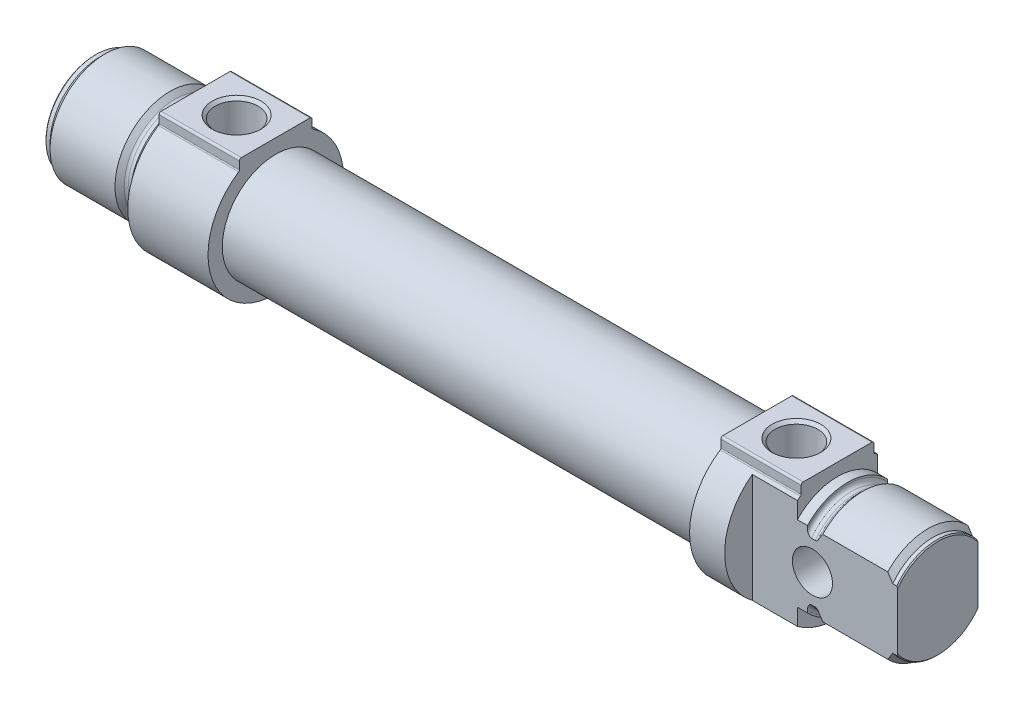
SolidWorks part; units mm, degrees
ref_plane "Front Plane" through (0, 0, 0) normal (0, 0, 1) x (1, 0, 0)
ref_plane "Top Plane" through (0, 0, 0) normal (0, 1, 0) x (1, 0, 0)
ref_plane "Right Plane" through (0, 0, 0) normal (1, 0, 0) x (0, 0, -1)
sketch "Sketch1" plane through (0, 0, 0) normal (0, 0, 1) x (1, 0, 0)
  line L0 (0, 0) -> (0, 9.8)
  line L1 (0, 9.8) -> (0.2, 10)
  line L2 (0.2, 10) -> (1, 10)
  line L3 (1, 10) -> (2, 11)
  line L4 (2, 11) -> (14.95, 11)
  line L5 (14.95, 11) -> (15.8657, 10.0843)
  line L6 (16.4314, 9.85) -> (17.2, 9.85)
  line L7 (18, 10.65) -> (18, 11)
  line L8 (18, 11) -> (20, 11)
  line L9 (20, 11) -> (20, 0)
  line L10 (20, 0) -> (0, 0)
  line L11 (20, 0) -> (0, 0) construction
  arc A0 (15.8657, 10.0843) -> (16.4314, 9.85) centre (16.4314, 10.65) ccw
  arc A1 (17.2, 9.85) -> (18, 10.65) centre (17.2, 10.65) ccw
revolve "Revolve1" add sketch "Sketch1" angle 360 about L11 reverse direction yes
cosmetic thread "Cosmetic Thread1" parameters "D1"=13.87, "D2"=20.16
ref_plane "Plane1" through (28.7, 0, 0) normal (1, 0, 0) x (0, 0, -1)
ref_plane "Plane2" through (10.5, 0, 0) normal (1, 0, 0) x (0, 0, -1)
ref_plane "Plane3" through (0, -14, 0) normal (0, 1, 0) x (1, 0, 0)
ref_plane "Plane4" through (0, 13, 0) normal (0, 1, 0) x (1, 0, 0)
ref_plane "Plane5" through (0, 0, 0) normal (0, 1, 0) x (1, 0, 0)
ref_plane "Plane6" through (0, 0, 0) normal (0, 1, 0) x (1, 0, 0)
ref_plane "Plane7" through (20, 0, 0) normal (1, 0, 0) x (0, 0, -1)
ref_plane "Plane8" through (20, 0, 0) normal (1, 0, 0) x (0, 0, -1)
ref_plane "Plane9" through (33, 0, 0) normal (1, 0, 0) x (0, 0, -1)
ref_plane "Plane10" through (24.5, 0, 0) normal (1, 0, 0) x (0, 0, -1)
ref_plane "Plane11" through (44.5, 0, 0) normal (1, 0, 0) x (0, 0, -1)
sketch "Sketch2" plane through (20, 0, 0) normal (1, 0, 0) x (0, 0, -1)
  line L0 (7.25, 11.5515) -> (7.25, 13.1)
  line L1 (6.85, 13.5) -> (-6.85, 13.5)
  line L2 (-7.25, 13.1) -> (-7.25, 11.5515)
  arc A0 (-7.3859, 11.3004) -> (7.3859, 11.3004) centre (0, 0) ccw
  arc A1 (7.3859, 11.3004) -> (7.25, 11.5515) centre (7.55, 11.5515) cw
  arc A2 (7.25, 13.1) -> (6.85, 13.5) centre (6.85, 13.1) ccw
  arc A3 (-6.85, 13.5) -> (-7.25, 13.1) centre (-6.85, 13.1) ccw
  arc A4 (-7.25, 11.5515) -> (-7.3859, 11.3004) centre (-7.55, 11.5515) cw
extrude "Boss-Extrude1" add sketch "Sketch2" along normal blind 16
ref_plane "Plane12" through (32.5, 0, 0) normal (1, 0, 0) x (0, 0, -1)
ref_plane "Plane13" through (0, 0, 0) normal (0, 0, 1) x (1, 0, 0)
ref_plane "Plane14" through (0, 0, -8.5) normal (0, 0, 1) x (1, 0, 0)
ref_plane "Plane15" through (0, 0, 0) normal (0, 1, 0) x (1, 0, 0)
ref_plane "Plane16" through (0, 6.9, 0) normal (0, 1, 0) x (1, 0, 0)
ref_plane "Plane17" through (0, 0, -6.6) normal (0, 0, 1) x (1, 0, 0)
ref_plane "Plane18" through (0, 0, 0) normal (0, 1, 0) x (1, 0, 0)
ref_plane "Plane19" through (0, 6.9, 0) normal (0, 1, 0) x (1, 0, 0)
ref_plane "Plane20" through (0, 7.8206, -1.379) normal (0, 0.9848, -0.1736) x (1, 0, 0)
ref_plane "Plane21" through (0, 6.3434, -1.1185) normal (0, 0.9848, -0.1736) x (1, 0, 0)
sketch "Sketch3" plane through (0, 0, 0) normal (0, 0, 1) x (1, 0, 0)
  line L0 (36, 0) -> (36, 10.65)
  line L1 (36, 10.65) -> (132, 10.65)
  line L2 (132, 10.65) -> (132, 0)
  line L3 (132, 0) -> (36, 0)
  line L4 (132, 0) -> (36, 0) construction
revolve "Revolve2" add sketch "Sketch3" angle 360 about L4 reverse direction yes
ref_plane "Plane22" through (132, 0, 0) normal (1, 0, 0) x (0, 0, -1)
sketch "Sketch4" plane through (132, 0, 0) normal (1, 0, 0) x (0, 0, -1)
  line L0 (7.25, 11.5515) -> (7.25, 13.1)
  line L1 (6.85, 13.5) -> (-6.85, 13.5)
  line L2 (-7.25, 13.1) -> (-7.25, 11.5515)
  arc A0 (-7.3859, 11.3004) -> (7.3859, 11.3004) centre (0, 0) ccw
  arc A1 (7.3859, 11.3004) -> (7.25, 11.5515) centre (7.55, 11.5515) cw
  arc A2 (7.25, 13.1) -> (6.85, 13.5) centre (6.85, 13.1) ccw
  arc A3 (-6.85, 13.5) -> (-7.25, 13.1) centre (-6.85, 13.1) ccw
  arc A4 (-7.25, 11.5515) -> (-7.3859, 11.3004) centre (-7.55, 11.5515) cw
extrude "Boss-Extrude2" add sketch "Sketch4" along normal blind 16
ref_plane "Plane23" through (135.8, 0, 0) normal (1, 0, 0) x (0, 0, -1)
ref_plane "Plane24" through (135.5, 0, 0) normal (1, 0, 0) x (0, 0, -1)
ref_plane "Plane25" through (0, 0, 6.6) normal (0, 0, 1) x (1, 0, 0)
ref_plane "Plane26" through (0, 0, 0) normal (0, 1, 0) x (1, 0, 0)
ref_plane "Plane27" through (0, 6.9, 0) normal (0, 1, 0) x (1, 0, 0)
ref_plane "Plane28" through (0, 7.8206, 1.379) normal (0, 0.9848, 0.1736) x (1, 0, 0)
ref_plane "Plane29" through (0, 6.3434, 1.1185) normal (0, 0.9848, 0.1736) x (1, 0, 0)
ref_plane "Plane30" through (195, 0, 0) normal (1, 0, 0) x (0, 0, -1)
sketch "Sketch5" plane through (0, 0, 0) normal (0, 0, 1) x (1, 0, 0)
  line L0 (148, 0) -> (148, 11)
  line L1 (148, 11) -> (150, 11)
  line L2 (150, 11) -> (150, 10.65)
  line L3 (150.8, 9.85) -> (151.5686, 9.85)
  line L4 (152.1343, 10.0843) -> (153.05, 11)
  line L5 (153.05, 11) -> (166, 11)
  line L6 (166, 11) -> (167, 10)
  line L7 (167, 10) -> (167.8, 10)
  line L8 (167.8, 10) -> (168, 9.8)
  line L9 (168, 9.8) -> (168, 0)
  line L10 (168, 0) -> (148, 0)
  line L11 (168, 0) -> (148, 0) construction
  arc A0 (150, 10.65) -> (150.8, 9.85) centre (150.8, 10.65) ccw
  arc A1 (151.5686, 9.85) -> (152.1343, 10.0843) centre (151.5686, 10.65) ccw
revolve "Revolve3" add sketch "Sketch5" angle 360 about L11 reverse direction yes
cosmetic thread "Cosmetic Thread2" parameters "D1"=12.87, "D2"=20.16
ref_plane "Plane31" through (182, 0, 0) normal (1, 0, 0) x (0, 0, -1)
ref_plane "Plane32" through (190.5, 0, 0) normal (1, 0, 0) x (0, 0, -1)
ref_plane "Plane33" through (170.5, 0, 0) normal (1, 0, 0) x (0, 0, -1)
sketch "Sketch6" plane through (0, 0, 0) normal (0, 1, 0) x (1, 0, 0)
  line L0 (139, 24) -> (139, 8)
  line L1 (139, 8) -> (168, 8)
  line L2 (168, 8) -> (168, -8)
  line L3 (168, -8) -> (139, -8)
  line L4 (139, -8) -> (139, -24)
  line L5 (139, -24) -> (184, -24)
  line L6 (184, -24) -> (184, 24)
  line L7 (184, 24) -> (139, 24)
extrude "Cut-Extrude1" cut sketch "Sketch6" along normal blind 13.5 and the other way blind 13.5
ref_plane "Plane34" through (151, 0, 0) normal (1, 0, 0) x (0, 0, -1)
sketch "Sketch7" plane through (151, 0, 0) normal (1, 0, 0) x (0, 0, -1)
  line L0 (-8, 0) -> (-8, 4)
  line L1 (-8, 4) -> (8, 4)
  line L2 (8, 4) -> (8, 0)
  line L3 (8, 0) -> (-8, 0)
  line L4 (8, 0) -> (-8, 0) construction
revolve "Cut-Revolve1" cut sketch "Sketch7" angle 360 about L4 reverse direction yes
hole_wizard "Hole1" positions "Sketch9" profile "Sketch8" legacy
sketch "Sketch9" plane through (0, 13.5, 0) normal (0, 1, 0) x (1, 0, 0)
  point P0 (28.2, 0)
sketch "Sketch8" plane through (28.2, 13.5, 0) normal (1, 0, 0) x (0, 0, 1)
  line L0 (0, 0) -> (0, 13.5)
  line L1 (0, 13.5) -> (4.283, 13.5)
  line L2 (4.283, 13.5) -> (4.283, 0.581)
  line L3 (4.283, 0.581) -> (4.864, 0)
  line L4 (4.864, 0) -> (0, 0)
  line L5 (0, -6.4453) -> (0, 115.525) construction
  line L6 (-4.283, 0.581) -> (-4.864, 0) construction
  dimension "Diameter" = 8.566
  dimension "Depth" = 13.5
  dimension "C-Sink Angle" = 90
  dimension "C-Sink Diameter" = 9.728
cosmetic thread "Cosmetic Thread3" parameters "D1"=9.5, "D2"=9.728
hole_wizard "Hole2" positions "Sketch11" profile "Sketch10" legacy
sketch "Sketch11" plane through (0, 13.5, 0) normal (0, 1, 0) x (1, 0, 0)
  point P0 (139.8, 0)
sketch "Sketch10" plane through (139.8, 13.5, 0) normal (1, 0, 0) x (0, 0, 1)
  line L0 (0, 0) -> (0, 18.4728)
  line L1 (0, 18.4728) -> (4.283, 16)
  line L2 (4.283, 16) -> (4.283, 0.581)
  line L3 (4.283, 0.581) -> (4.864, 0)
  line L4 (4.864, 0) -> (0, 0)
  line L5 (0, -14.3089) -> (0, 102.4216) construction
  line L6 (0, 18.4728) -> (-4.283, 16) construction
  line L7 (-4.283, 0.581) -> (-4.864, 0) construction
  dimension "Diameter" = 8.566
  dimension "Depth" = 16
  dimension "C-Sink Diameter" = 9.728
  dimension "C-Sink Angle" = 90
  dimension "Drill Angle" = 120
cosmetic thread "Cosmetic Thread4" parameters "D1"=8, "D2"=9.728
sketch "Sketch12" plane through (0, 0, 0) normal (0, 0, 1) x (1, 0, 0)
  line L0 (-4, 0) -> (-4, 4)
  line L1 (-4, 4) -> (50.3, 4)
  line L2 (50.3, 4) -> (50.3, 10)
  line L3 (50.3, 10) -> (115.3, 10)
  line L4 (115.3, 10) -> (115.3, 0)
  line L5 (115.3, 0) -> (-4, 0)
  line L6 (115.3, 0) -> (-4, 0) construction
revolve "Cut-Revolve2" cut sketch "Sketch12" angle 360 about L6 reverse direction yes
ref_plane "Plane35" through (-4, 0, 0) normal (1, 0, 0) x (0, 0, -1)
ref_plane "Plane36" through (0, 13.5, 0) normal (0, 1, 0) x (1, 0, 0)
ref_plane "Plane37" through (6.5, 0, 0) normal (1, 0, 0) x (0, 0, -1)
ref_plane "Plane38" through (0, 0, 0) normal (1, 0, 0) x (0, 0, -1)
ref_plane "Plane39" through (20, 0, 0) normal (1, 0, 0) x (0, 0, -1)
ref_plane "Plane40" through (148, 0, 0) normal (1, 0, 0) x (0, 0, -1)
ref_plane "Plane41" through (20, 0, 0) normal (1, 0, 0) x (0, 0, -1)
ref_plane "Plane42" through (0, 13.5, 0) normal (0, 1, 0) x (1, 0, 0)
ref_plane "Plane43" through (45.5, 0, 0) normal (1, 0, 0) x (0, 0, -1)
ref_plane "Plane44" through (122.5, 0, 0) normal (1, 0, 0) x (0, 0, -1)
ref_plane "Plane45" through (0, 0, 0) normal (0, 0, 1) x (1, 0, 0)
ref_plane "Plane46" through (20, 0, 0) normal (1, 0, 0) x (0, 0, -1)
ref_plane "Plane47" through (0, 13.5, 0) normal (0, 1, 0) x (1, 0, 0)
ref_plane "FDT_FRONT XY" through (20, 0, 0) normal (1, 0, 0) x (0, 0, -1)
ref_plane "FDT_FRONT XZ" through (0, 0, 0) normal (0, -1, 0) x (-1, 0, 0)
ref_plane "FDT_FRONT YZ" through (0, 0, 0) normal (0, 0, -1) x (-1, 0, 0)
ref_axis "FDT_FRONT X" through (20, 0, 80.9) along (0, 0, -1)
ref_axis "FDT_FRONT Y" through (20, -50, 0) along (0, 1, 0)
ref_axis "FDT_FRONT Z" through (80.9, 0, 0) along (-1, 0, 0)
sketch3d "FDT_FRONT"
  point P0 (20, 0, 0)
ref_plane "FDT_QSFRONT XY" through (0, 13.5, 0) normal (0, 1, 0) x (1, 0, 0)
ref_plane "FDT_QSFRONT XZ" through (28.2, 0, 0) normal (-1, 0, 0) x (0, 0, 1)
ref_plane "FDT_QSFRONT YZ" through (0, 0, 0) normal (0, 0, 1) x (1, 0, 0)
ref_axis "FDT_QSFRONT X" through (28.2, 13.5, -50) along (0, 0, 1)
ref_axis "FDT_QSFRONT Y" through (-80.9, 13.5, 0) along (1, 0, 0)
ref_axis "FDT_QSFRONT Z" through (28.2, 50, 0) along (0, -1, 0)
sketch3d "FDT_QSFRONT"
  point P0 (28.2, 13.5, 0)
ref_plane "FDT_QSREAR XY" through (0, 13.5, 0) normal (0, 1, 0) x (1, 0, 0)
ref_plane "FDT_QSREAR XZ" through (139.8, 0, 0) normal (-1, 0, 0) x (0, 0, 1)
ref_plane "FDT_QSREAR YZ" through (0, 0, 0) normal (0, 0, 1) x (1, 0, 0)
ref_axis "FDT_QSREAR X" through (139.8, 13.5, -50) along (0, 0, 1)
ref_axis "FDT_QSREAR Y" through (-80.9, 13.5, 0) along (1, 0, 0)
ref_axis "FDT_QSREAR Z" through (139.8, 50, 0) along (0, -1, 0)
sketch3d "FDT_QSREAR"
  point P0 (139.8, 13.5, 0)
ref_plane "FDT_REAR XY" through (148, 0, 0) normal (-1, 0, 0) x (0, 0, 1)
ref_plane "FDT_REAR XZ" through (0, 0, 0) normal (0, 1, 0) x (1, 0, 0)
ref_plane "FDT_REAR YZ" through (0, 0, 0) normal (0, 0, -1) x (-1, 0, 0)
ref_axis "FDT_REAR X" through (148, 0, 80.9) along (0, 0, -1)
ref_axis "FDT_REAR Y" through (148, 50, 0) along (0, -1, 0)
ref_axis "FDT_REAR Z" through (-80.9, 0, 0) along (1, 0, 0)
sketch3d "FDT_REAR"
  point P0 (148, 0, 0)
ref_plane "FDT_SMBR1 XY" through (45.5, 0, 0) normal (-1, 0, 0) x (0, 0, 1)
ref_plane "FDT_SMBR1 XZ" through (0, 0, 0) normal (0, -1, 0) x (-1, 0, 0)
ref_plane "FDT_SMBR1 YZ" through (0, 0, 0) normal (0, 0, 1) x (1, 0, 0)
ref_axis "FDT_SMBR1 X" through (45.5, 0, -80.9) along (0, 0, 1)
ref_axis "FDT_SMBR1 Y" through (45.5, -50, 0) along (0, 1, 0)
ref_axis "FDT_SMBR1 Z" through (-80.9, 0, 0) along (1, 0, 0)
sketch3d "FDT_SMBR1"
  point P0 (45.5, 0, 0)
ref_plane "FDT_SMBR2 XY" through (122.5, 0, 0) normal (-1, 0, 0) x (0, 0, 1)
ref_plane "FDT_SMBR2 XZ" through (0, 0, 0) normal (0, -1, 0) x (-1, 0, 0)
ref_plane "FDT_SMBR2 YZ" through (0, 0, 0) normal (0, 0, 1) x (1, 0, 0)
ref_axis "FDT_SMBR2 X" through (122.5, 0, -80.9) along (0, 0, 1)
ref_axis "FDT_SMBR2 Y" through (122.5, -50, 0) along (0, 1, 0)
ref_axis "FDT_SMBR2 Z" through (-80.9, 0, 0) along (1, 0, 0)
sketch3d "FDT_SMBR2"
  point P0 (122.5, 0, 0)
ref_plane "FDT_SWIVELAXIS XY" through (0, 0, 0) normal (0, 0, 1) x (1, 0, 0)
ref_plane "FDT_SWIVELAXIS XZ" through (0, 0, 0) normal (0, -1, 0) x (-1, 0, 0)
ref_plane "FDT_SWIVELAXIS YZ" through (151, 0, 0) normal (1, 0, 0) x (0, 0, -1)
ref_axis "FDT_SWIVELAXIS X" through (-80.9, 0, 0) along (1, 0, 0)
ref_axis "FDT_SWIVELAXIS Y" through (151, -50, 0) along (0, 1, 0)
ref_axis "FDT_SWIVELAXIS Z" through (151, 0, 80.9) along (0, 0, -1)
sketch3d "FDT_SWIVELAXIS"
  point P0 (151, 0, 0)
ref_plane "NUT XY" through (6.5, 0, 0) normal (1, 0, 0) x (0, 0, -1)
ref_plane "NUT XZ" through (0, 0, 0) normal (0, -1, 0) x (-1, 0, 0)
ref_plane "NUT YZ" through (0, 0, 0) normal (0, 0, -1) x (-1, 0, 0)
ref_axis "NUT X" through (6.5, 0, 80.9) along (0, 0, -1)
ref_axis "NUT Y" through (6.5, -50, 0) along (0, 1, 0)
ref_axis "NUT Z" through (80.9, 0, 0) along (-1, 0, 0)
sketch3d "NUT"
  point P0 (6.5, 0, 0)
ref_plane "ZR XY" through (0, 0, 0) normal (1, 0, 0) x (0, 0, -1)
ref_plane "ZR XZ" through (0, 0, 0) normal (0, -1, 0) x (-1, 0, 0)
ref_plane "ZR YZ" through (0, 0, 0) normal (0, 0, -1) x (-1, 0, 0)
ref_axis "ZR X" through (0, 0, 80.9) along (0, 0, -1)
ref_axis "ZR Y" through (0, -50, 0) along (0, 1, 0)
ref_axis "ZR Z" through (80.9, 0, 0) along (-1, 0, 0)
sketch3d "ZR"
  point P0 (0, 0, 0)
ref_plane "ZYL XY" through (20, 0, 0) normal (1, 0, 0) x (0, 0, -1)
ref_plane "ZYL XZ" through (0, 0, 0) normal (0, -1, 0) x (-1, 0, 0)
ref_plane "ZYL YZ" through (0, 0, 0) normal (0, 0, -1) x (-1, 0, 0)
ref_axis "ZYL X" through (20, 0, 80.9) along (0, 0, -1)
ref_axis "ZYL Y" through (20, -50, 0) along (0, 1, 0)
ref_axis "ZYL Z" through (80.9, 0, 0) along (-1, 0, 0)
sketch3d "ZYL"
  point P0 (20, 0, 0)
